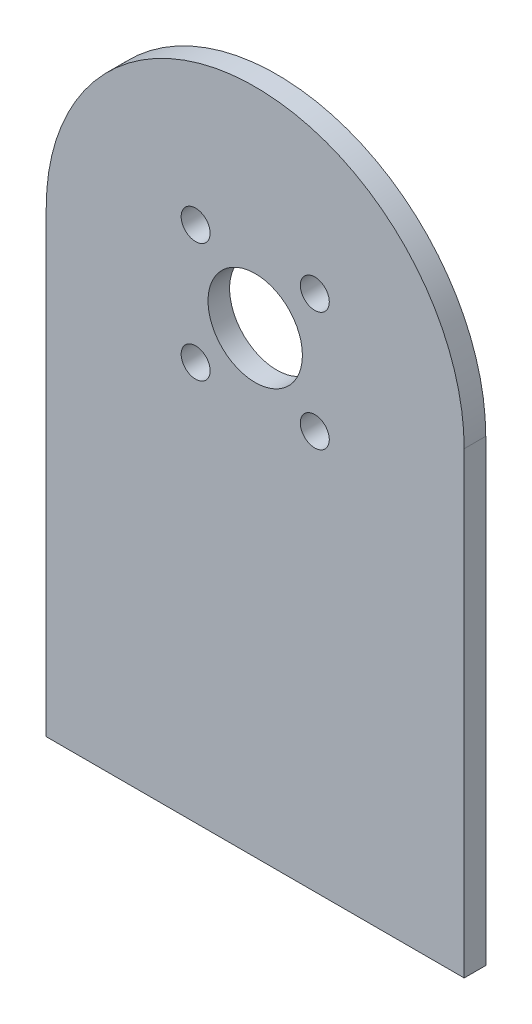
SolidWorks part; units mm, degrees
material "AISI 304"
ref_plane "Front Plane" through (0, 0, 0) normal (0, 0, 1) x (1, 0, 0)
ref_plane "Top Plane" through (0, 0, 0) normal (0, 1, 0) x (1, 0, 0)
ref_plane "Right Plane" through (0, 0, 0) normal (1, 0, 0) x (0, 0, -1)
sketch "Sketch1" plane through (0, 0, 0) normal (0, 0, 1) x (1, 0, 0)
  line L1 (-75, 80) -> (75, 80)
  line L2 (-75, 80) -> (-75, -80)
  line L3 (-75, -80) -> (75, -80)
  line L4 (75, 80) -> (75, -80)
  line L5 (-75, 80) -> (75, -80) construction
  line L6 (-75, -80) -> (75, 80) construction
  point P0 (0, 0)
  dimension "D1" = 150
  dimension "D2" = 160
extrude "Boss-Extrude1" add sketch "Sketch1" along normal blind 3.2
sketch "Sketch2" plane through (0, 0, 3.2) normal (0, 0, 1) x (1, 0, 0)
  line L0 (-75, -80) -> (75, -80) construction
  circle A0 centre (0, -12) radius 7
  dimension "D1" = 14
  dimension "D2" = 68
extrude "Cut-Extrude1" cut sketch "Sketch2" against normal up to next
sketch "Sketch3" plane through (0, 0, 3.2) normal (0, 0, 1) x (1, 0, 0)
  line L0 (-83.9315, 71.9315) -> (0, -12) construction
  line L1 (0, -12) -> (-75, -12) construction
  line L2 (-75, 80) -> (-75, -80) construction
  circle A0 centre (-8.8388, -3.1612) radius 2.15
  dimension "D1" = 4.3
  dimension "D2" = 12.5
  dimension "D3" = 45
extrude "Cut-Extrude2" cut sketch "Sketch3" against normal through all
pattern_circular "CirPattern1" count 4 every 90 about axis through (0, -12, 3.2) along (0, 0, 1) of "Cut-Extrude2"
sketch "Sketch5" plane through (0, 0, 3.2) normal (0, 0, 1) x (1, 0, 0)
  line L0 (-75, -80) -> (75, -80) construction
  line L1 (-31, -80) -> (31, -80)
  line L5 (31, -80) -> (31, -12)
  line L7 (-31, -12) -> (-31, -80)
  arc A4 (31, -12) -> (-31, -12) centre (0, -12) ccw
  dimension "D1" = 68
  dimension "D2" = 31
extrude "Cut-Extrude4" cut sketch "Sketch5" against normal blind 10 flip side to cut
sketch "Sketch6" plane through (0, 0, 3.2) normal (0, 0, 1) x (1, 0, 0)
  line L0 (0, -12) -> (0, 19) construction
  arc A0 (31, -12) -> (-31, -12) centre (0, -12) ccw construction
